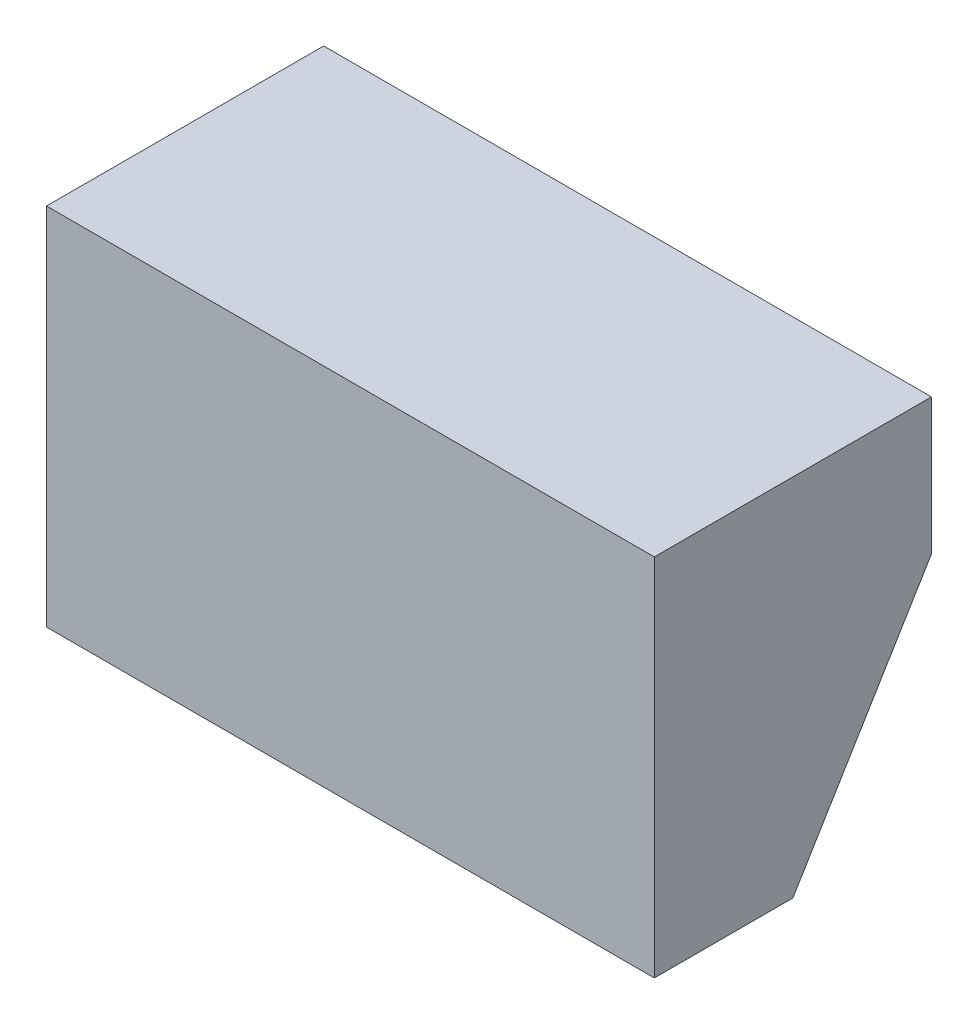
SolidWorks part; units mm, degrees
ref_plane "前视基准面" through (0, 0, 0) normal (0, 0, 1) x (1, 0, 0)
ref_plane "上视基准面" through (0, 0, 0) normal (0, 1, 0) x (1, 0, 0)
ref_plane "右视基准面" through (0, 0, 0) normal (1, 0, 0) x (0, 0, -1)
sketch "Sketch1" plane through (0, 0, 0) normal (0, 0, 1) x (1, 0, 0)
  line L1 (-125, -75) -> (125, -75)
  line L2 (-125, -75) -> (-125, 75)
  line L3 (-125, 75) -> (125, 75)
  line L4 (125, -75) -> (125, 75)
  line L5 (-125, -75) -> (125, 75) construction
  line L6 (-125, 75) -> (125, -75) construction
  point P0 (0, 0)
  dimension "D1" = 250
  dimension "D2" = 150
extrude "Boss-Extrude1" add sketch "Sketch1" along normal blind 114
sketch "sketchCenterLine" plane through (0, 0, 114) normal (0, 0, 1) x (1, 0, 0)
  line L0 (0, 0) -> (-160.1488, 0) construction
  line L1 (-170, 12.5) -> (-115, 12.5)
  line L2 (-97.3223, 19.8223) -> (-69.467, 47.6777)
  line L3 (-51.7893, 55) -> (70, 55)
  line L4 (95, 30) -> (95, -30)
  line L5 (70, -55) -> (-51.7893, -55)
  line L6 (-69.467, -47.6777) -> (-97.3223, -19.8223)
  line L7 (-115, -12.5) -> (-170, -12.5)
  line L8 (-125, 75) -> (-125, -75) construction
  arc A0 (70, -55) -> (95, -30) centre (70, -30) ccw
  arc A1 (95, 30) -> (70, 55) centre (70, 30) ccw
  arc A2 (-115, 12.5) -> (-97.3223, 19.8223) centre (-115, 37.5) ccw
  arc A3 (-97.3223, -19.8223) -> (-115, -12.5) centre (-115, -37.5) ccw
  arc A4 (-51.7893, -55) -> (-69.467, -47.6777) centre (-51.7893, -30) cw
  arc A5 (-69.467, 47.6777) -> (-51.7893, 55) centre (-51.7893, 30) cw
  point P10 (-141.1441, 19.6999)
  point P12 (-166.6382, 20.1634)
  point P13 (0, 0)
  point P24 (-62.1447, -55)
  point P27 (-62.1447, 55)
  point P30 (-70.1294, 47.6777)
  point P31 (-69.467, -45.3239)
  point P32 (0, 0)
  dimension "D1" = 25
  dimension "D2" = 25
  dimension "D8" = 10
  dimension "D3" = 95
  dimension "D4" = 110
  dimension "D5" = 25
  dimension "D6" = 45
  dimension "D7" = 45
sketch3d "3DSketch1"
  line L0 (125, -75, 114) -> (125, -75, 0) construction
  line L1 (125, -75, 0) -> (125, 75, 0) construction
  line L2 (-125, -75, 0) -> (125, -75, 0) construction
  point P0 (125, -75, 57)
  point P1 (125, 19.0618, 0)
  point P4 (42.2925, -75, 0)
ref_plane "Plane1" through (27.9069, -24.5383, -40.4932) normal (-0.5078, 0.4465, 0.7368) x (0.8615, 0.2632, 0.4343)
sketch "Sketch4" plane through (27.9069, -24.5383, -40.4932) normal (-0.5078, 0.4465, 0.7368) x (0.8615, 0.2632, 0.4343)
  line L1 (-16.3307, -143.8321) -> (142.4953, -143.8321)
  line L2 (-16.3307, -143.8321) -> (-16.3307, 25.2667)
  line L3 (-16.3307, 25.2667) -> (142.4953, 25.2667)
  line L4 (142.4953, -143.8321) -> (142.4953, 25.2667)
  point P4 (142.4953, -143.8321)
extrude "Cut-Extrude1" cut sketch "Sketch4" against normal blind 114
